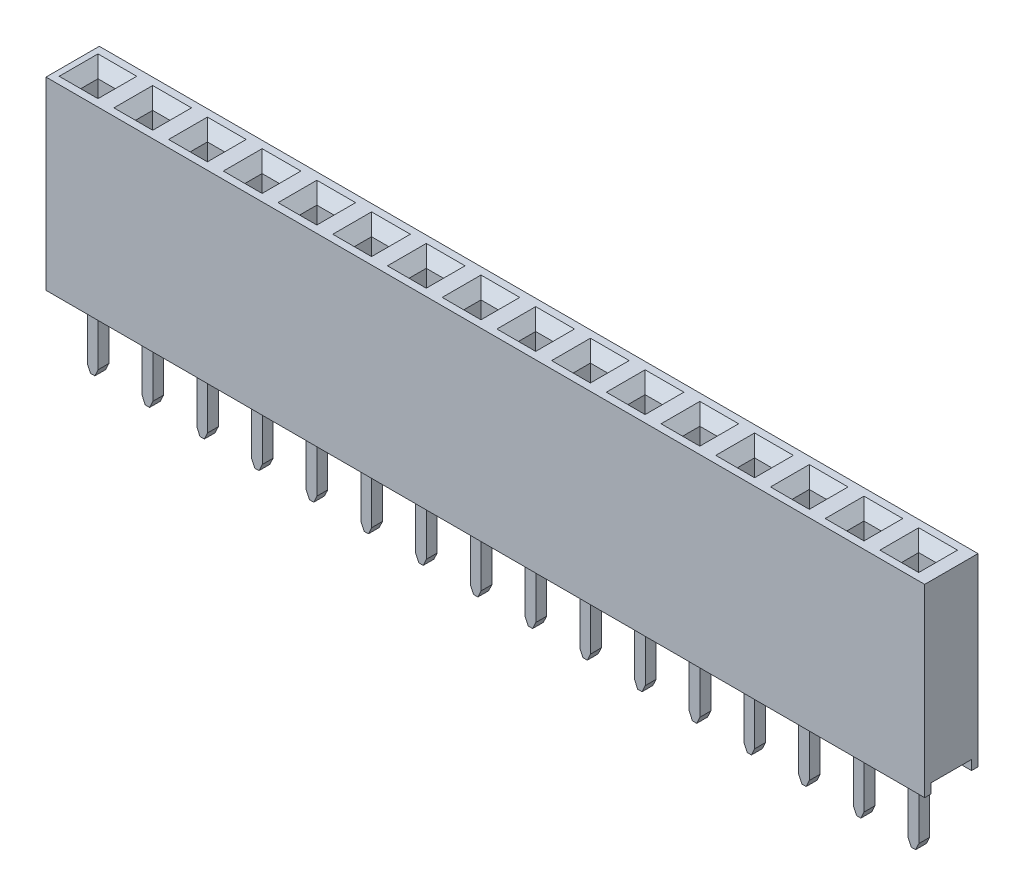
SolidWorks part; units mm, degrees
note: The reader was unsure of these and kept them because the rebuilt part matched: shared geometry of "Sketch9<3>".
ref_plane "Front" through (0, 0, 0) normal (0, 0, 1) x (1, 0, 0)
ref_plane "Top" through (0, 0, 0) normal (0, 1, 0) x (1, 0, 0)
ref_plane "Right" through (0, 0, 0) normal (1, 0, 0) x (0, 0, -1)
sketch "Sketch1" plane through (0, 0, 0) normal (0, 0, 1) x (1, 0, 0)
  line L1 (20.395, -4.2875) -> (-20.395, -4.2875)
  line L2 (20.395, -4.2875) -> (20.395, 4.2875)
  line L3 (20.395, 4.2875) -> (-20.395, 4.2875)
  line L4 (-20.395, -4.2875) -> (-20.395, 4.2875)
  line L5 (20.395, -4.2875) -> (-20.395, 4.2875) construction
  line L6 (20.395, 4.2875) -> (-20.395, -4.2875) construction
  point P0 (0, 0)
  dimension "D1" = 40.79
  dimension "D2" = 8.575
extrude "Boss-Extrude1" add sketch "Sketch1" along normal mid plane 2.475
sketch "Sketch2" plane through (0, 0, 0) normal (1, 0, 0) x (0, 0, -1)
  line L0 (-0.9375, -4.2875) -> (0.9375, -4.2875)
  line L1 (-1.2375, -4.2875) -> (1.2375, -4.2875) construction
  line L2 (0.9375, -4.2875) -> (0.9375, -3.8396)
  line L3 (0.9375, -3.8396) -> (-0.9375, -3.8396)
  line L4 (-0.9375, -3.8396) -> (-0.9375, -4.2875)
  line L5 (1.2375, -4.2875) -> (1.2375, 4.2875) construction
  line L6 (-1.2375, -4.2875) -> (-1.2375, 4.2875) construction
  dimension "D1" = 0.3
  dimension "D2" = 0.3
extrude "Cut-Extrude1" cut sketch "Sketch2" against normal mid plane 100
sketch "Sketch4" plane through (0, 4.2875, 0) normal (0, 1, 0) x (1, 0, 0)
  line L0 (-20.395, 0) -> (20.395, 0) construction
  line L1 (-20.395, -1.2375) -> (-20.395, 1.2375) construction
  line L2 (20.395, -1.2375) -> (20.395, 1.2375) construction
  line L4 (-20.095, 0.875) -> (-18.345, 0.875)
  line L5 (-20.095, 0.875) -> (-20.095, -0.875)
  line L6 (-20.095, -0.875) -> (-18.345, -0.875)
  line L7 (-18.345, 0.875) -> (-18.345, -0.875)
  line L8 (-20.095, 0.875) -> (-18.345, -0.875) construction
  line L9 (-20.095, -0.875) -> (-18.345, 0.875) construction
  line L10 (-19.62, 0.4) -> (-18.82, 0.4)
  line L11 (-19.62, 0.4) -> (-19.62, -0.4)
  line L12 (-19.62, -0.4) -> (-18.82, -0.4)
  line L13 (-18.82, 0.4) -> (-18.82, -0.4)
  line L14 (-19.62, 0.4) -> (-18.82, -0.4) construction
  line L15 (-19.62, -0.4) -> (-18.82, 0.4) construction
  point P6 (-19.22, 0)
  point P11 (-19.22, 0)
  dimension "D1" = 1.75
  dimension "D2" = 0.8
  dimension "D3" = 0.3
extrude "Cut-Extrude2" cut sketch "Sketch4" against normal blind 1.5 contours L13 L10 L11 L12
chamfer "Chamfer1" distance 0.5 angle 45 4 edges at (-19.22, 4.2875, -0.4) (-19.62, 4.2875, 0) (-19.22, 4.2875, 0.4) (-18.82, 4.2875, 0)
sketch "Sketch5" plane through (0, 0, 0) normal (0, 1, 0) x (1, 0, 0)
  line L1 (-20.12, 0.9) -> (-18.32, 0.9)
  line L2 (-20.12, 0.9) -> (-20.12, -0.9)
  line L3 (-20.12, -0.9) -> (-18.32, -0.9)
  line L4 (-18.32, 0.9) -> (-18.32, -0.9)
extrude "Cut-Extrude3" cut sketch "Sketch5" against normal blind 3 and the other way blind 3
sketch "Sketch9" plane through (0, 0, 0) normal (0, 0, 1) x (1, 0, 0)
  line L0 (-19.2134, 1.6839) -> (-19.2134, -6.1854) construction
  line L1 (-18.32, -1.2586) -> (-18.348, -1.1406)
  line L2 (-18.348, -1.1406) -> (-18.798, 1.5706)
  line L3 (-18.9294, 1.4044) -> (-18.7022, -1.9066)
  line L4 (-18.32, -1.2586) -> (-18.32, -2.6102)
  line L5 (-18.32, -2.6102) -> (-18.592, -2.9702)
  line L6 (-18.592, -2.9702) -> (-19.848, -2.9702)
  line L7 (-20.12, -2.6102) -> (-19.848, -2.9702)
  line L8 (-20.12, -1.2586) -> (-20.12, -2.6102)
  line L9 (-20.12, -1.2586) -> (-20.092, -1.1406)
  line L10 (-20.092, -1.1406) -> (-19.642, 1.5706)
  line L11 (-19.5106, 1.4044) -> (-19.7378, -1.9066)
  line L12 (-19.3134, -7.5787) -> (-19.1134, -7.5787)
  line L13 (-19.1134, -7.5787) -> (-18.9634, -7.257)
  line L14 (-18.9634, -7.257) -> (-18.9634, -2.9702)
  line L15 (-19.3134, -7.5787) -> (-19.4634, -7.257)
  line L16 (-19.4634, -7.257) -> (-19.4634, -2.9702)
  line L19 (-20.12, 3) -> (-20.12, -3) construction
  line L20 (-18.32, 3) -> (-18.32, -3) construction
  arc A0 (-18.798, 1.5706) -> (-18.9294, 1.4044) centre (-18.9392, 1.5472) ccw
  arc A1 (-18.7022, -1.9066) -> (-19.22, -2.3264) centre (-19.1087, -1.9345) cw
  arc A2 (-19.7378, -1.9066) -> (-19.22, -2.3264) centre (-19.3313, -1.9345) ccw
  arc A3 (-19.642, 1.5706) -> (-19.5106, 1.4044) centre (-19.5008, 1.5472) cw
  point P16 (-19.2134, -2.9702)
  point P24 (-19.4634, -4.2787)
extrude "Boss-Extrude4" add sketch "Sketch9" along normal mid plane 1.7 contours A1 L0 L6 L5 L4 L1 L2 A0 L3 | L0 A2 L11 A3 L10 L9 L8 L7 L6 | L14 L13 L12 L15 L16
extrude "Boss-Extrude5" add sketch "Sketch9<3>" along normal mid plane 0.5
sketch "Sketch9<3>" plane through (0, 0, 0) normal (0, 0, 1) x (1, 0, 0) same geometry as "Sketch9"
pattern_linear "LPattern1" count 16 spacing 2.54 along (1, 0, 0) of "Cut-Extrude2", "Chamfer1", "Cut-Extrude3", "Boss-Extrude4", "Boss-Extrude5"
sketch "Sketch10" plane through (0, -7.5787, 0) normal (0, -1, 0) x (1, 0, 0)
  circle A0 centre (-19.2134, 0) radius 0.1
